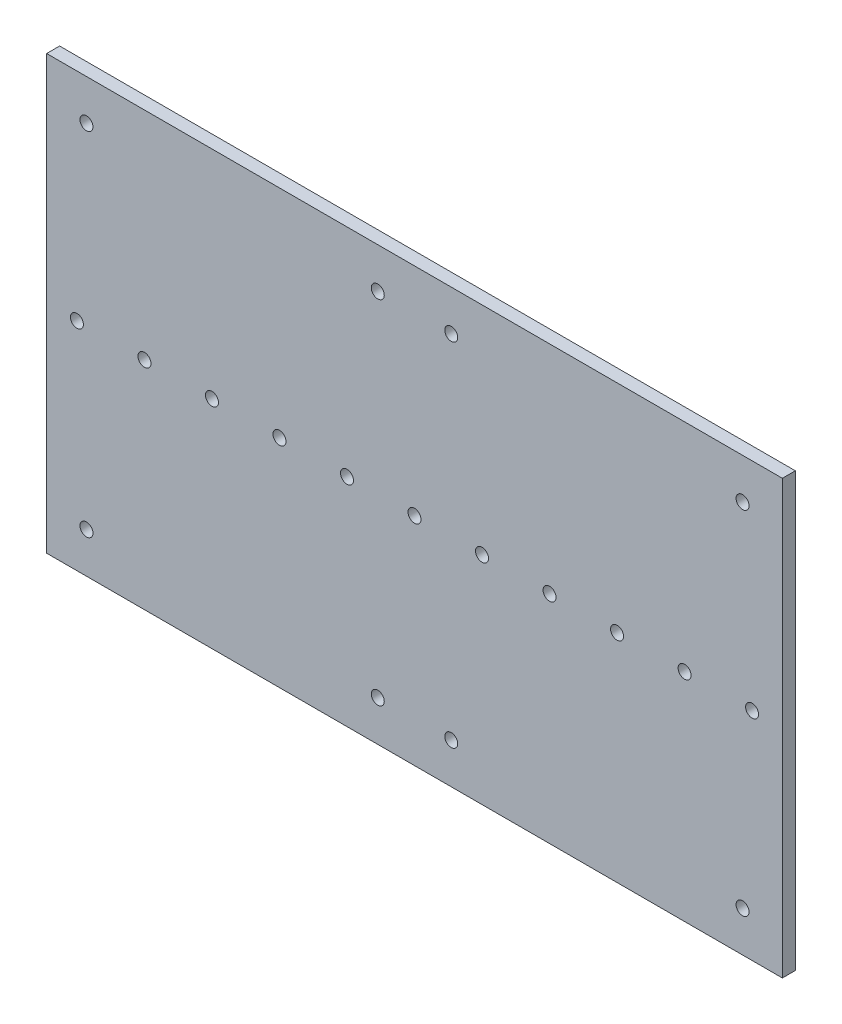
SolidWorks part; units mm, degrees
ref_plane "Front Plane" through (0, 0, 0) normal (0, 0, 1) x (1, 0, 0)
ref_plane "Top Plane" through (0, 0, 0) normal (0, 1, 0) x (1, 0, 0)
ref_plane "Right Plane" through (0, 0, 0) normal (1, 0, 0) x (0, 0, -1)
sketch "Sketch1" plane through (0, 0, 0) normal (0, 0, 1) x (1, 0, 0)
  line L1 (-85, 50) -> (85, 50)
  line L2 (-85, 50) -> (-85, -50)
  line L3 (-85, -50) -> (85, -50)
  line L4 (85, 50) -> (85, -50)
  line L5 (-85, 50) -> (85, -50) construction
  line L6 (-85, -50) -> (85, 50) construction
  point P0 (0, 0)
  dimension "D1" = 170
  dimension "D2" = 100
extrude "Boss-Extrude1" add sketch "Sketch1" along normal blind 3
sketch "Sketch2" plane through (0, 0, 3) normal (0, 0, 1) x (1, 0, 0)
  line L0 (-85, 0) -> (85, 0) construction
  line L5 (75.8, -40.64) -> (-75.8, 40.64) construction
  line L6 (75.8, 40.64) -> (-75.8, -40.64) construction
  line L16 (-85, 50) -> (-85, -50) construction
  line L17 (85, -50) -> (85, 50) construction
  circle A0 centre (-75.8, 40.64) radius 1.5
  circle A1 centre (-75.8, -40.64) radius 1.5
  circle A2 centre (75.8, 40.64) radius 1.5
  circle A3 centre (75.8, -40.64) radius 1.5
  circle A7 centre (-8.49, 40.64) radius 1.5
  circle A8 centre (-8.49, -40.64) radius 1.5
  circle A9 centre (8.49, 40.64) radius 1.5
  circle A10 centre (8.49, -40.64) radius 1.5
  circle A11 centre (0, 0) radius 1.5
  circle A12 centre (15.6, 0) radius 1.5
  circle A13 centre (31.2, 0) radius 1.5
  circle A14 centre (46.8, 0) radius 1.5
  circle A15 centre (62.4, 0) radius 1.5
  circle A16 centre (78, 0) radius 1.5
  circle A17 centre (-15.6, 0) radius 1.5
  circle A18 centre (-31.2, 0) radius 1.5
  circle A19 centre (-46.8, 0) radius 1.5
  circle A20 centre (-62.4, 0) radius 1.5
  circle A21 centre (-78, 0) radius 1.5
  point P0 (0, 0)
  dimension "D3" = 3
  dimension "D4" = 3
  dimension "D5" = 3
  dimension "D6" = 3
  dimension "D9" = 3
  dimension "D10" = 67.31
  dimension "D11" = 3
  dimension "D8" = 3
  dimension "D12" = 3
  dimension "D13" = 3
  dimension "D1" = 81.28
  dimension "D2" = 151.6
  dimension "D7" = 67.31
  dimension "D14" = 6
  dimension "D15" = 6
extrude "Cut-Extrude1" cut sketch "Sketch2" against normal blind 4
